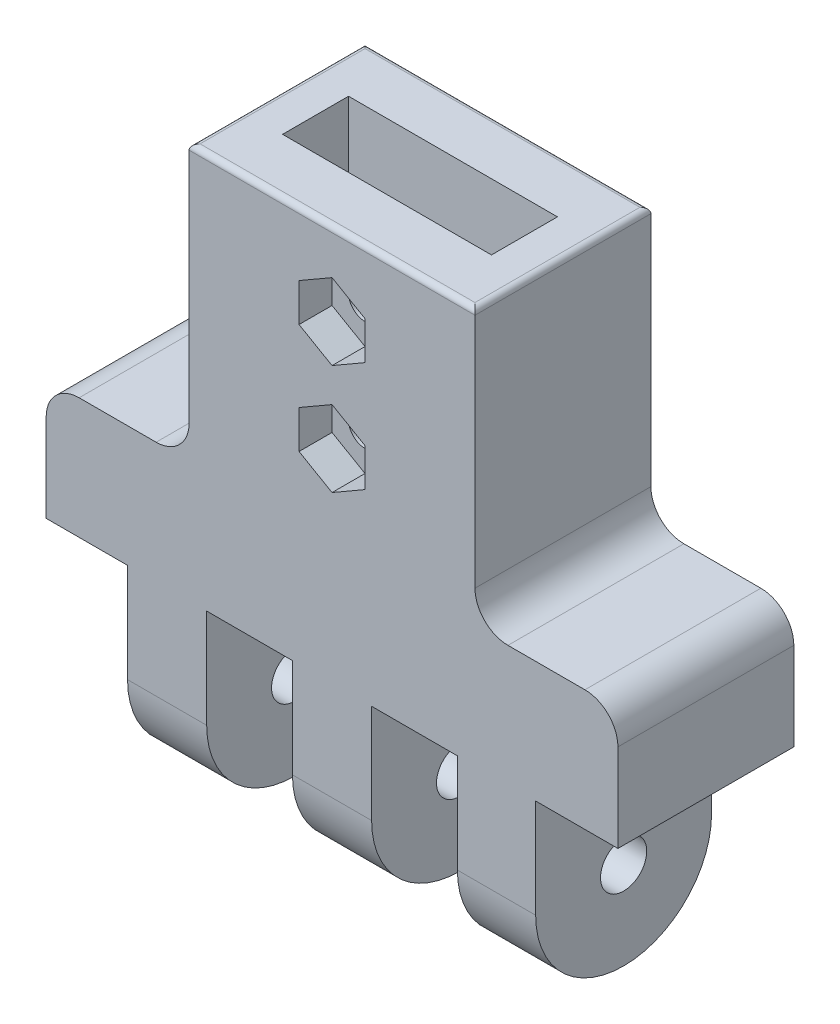
SolidWorks part; units mm, degrees
ref_plane "Front Plane" through (0, 0, 0) normal (0, 0, 1) x (1, 0, 0)
ref_plane "Top Plane" through (0, 0, 0) normal (0, 1, 0) x (1, 0, 0)
ref_plane "Right Plane" through (0, 0, 0) normal (1, 0, 0) x (0, 0, -1)
sketch "Sketch2" plane through (0, 0, 0) normal (1, 0, 0) x (0, 0, -1)
  line L2 (-8, 0) -> (-8, 20)
  line L3 (-8, 20) -> (8, 20)
  line L4 (8, 0) -> (8, 20)
  circle A0 centre (0, 0) radius 2.1
  arc A1 (-8, 0) -> (8, 0) centre (0, 0) ccw
  dimension "D1" = 16
  dimension "D2" = 4.2
  dimension "D3" = 20
extrude "Boss-Extrude1" add sketch "Sketch2" along normal mid plane 52
sketch "Sketch3" plane through (0, 0, 8) normal (0, 0, 1) x (1, 0, 0)
  line L0 (26, 0) -> (-26, 0) construction
  line L1 (-26, -9) -> (-18.6, -9)
  line L2 (-26, -9) -> (-26, 9)
  line L3 (-26, 9) -> (-18.6, 9)
  line L4 (-18.6, -9) -> (-18.6, 9)
  line L5 (-26, -9) -> (-18.6, 9) construction
  line L6 (-26, 9) -> (-18.6, -9) construction
  line L8 (-11.4, -9) -> (-3.6, -9)
  line L9 (-11.4, -9) -> (-11.4, 9)
  line L10 (-11.4, 9) -> (-3.6, 9)
  line L11 (-3.6, -9) -> (-3.6, 9)
  line L12 (-11.4, -9) -> (-3.6, 9) construction
  line L13 (-11.4, 9) -> (-3.6, -9) construction
  line L14 (3.6, -9) -> (11.4, -9)
  line L15 (3.6, -9) -> (3.6, 9)
  line L16 (3.6, 9) -> (11.4, 9)
  line L17 (11.4, -9) -> (11.4, 9)
  line L18 (3.6, -9) -> (11.4, 9) construction
  line L19 (3.6, 9) -> (11.4, -9) construction
  line L20 (-26, 20) -> (-26, 0) construction
  line L21 (26, 20) -> (26, 0) construction
  line L22 (18.519, -9) -> (26, -9)
  line L23 (18.519, -9) -> (18.519, 9)
  line L24 (18.519, 9) -> (26, 9)
  line L25 (26, -9) -> (26, 9)
  line L26 (18.519, -9) -> (26, 9) construction
  line L27 (18.519, 9) -> (26, -9) construction
  point P0 (-22.3, 0)
  point P7 (-7.5, 0)
  point P12 (7.5, 0)
  point P17 (-22.3, 9)
  point P20 (22.2595, 0)
  dimension "D1" = 9
  dimension "D4" = 7.2
  dimension "D6" = 7.2
  dimension "D2" = 7.8
  dimension "D3" = 14.6
extrude "Cut-Extrude1" cut sketch "Sketch3" against normal through all
ref_plane "Plane1" through (0, 20, 0) normal (0, 1, 0) x (1, 0, 0)
sketch "Sketch4" plane through (0, 20, 0) normal (0, 1, 0) x (1, 0, 0)
  line L0 (26, 8) -> (26, -8) construction
  line L1 (13, -8) -> (-13, -8)
  line L2 (13, -8) -> (13, 8)
  line L3 (13, 8) -> (-13, 8)
  line L4 (-13, -8) -> (-13, 8)
  line L5 (13, -8) -> (-13, 8) construction
  line L6 (13, 8) -> (-13, -8) construction
  line L8 (26, -8) -> (-26, -8) construction
  point P0 (0, 0)
  dimension "D1" = 26
  dimension "D2" = 16
  dimension "D3" = 26
extrude "Boss-Extrude2" add sketch "Sketch4" along normal blind 25
ref_plane "Plane2" through (0, 45, 0) normal (0, 1, 0) x (1, 0, 0)
sketch "Sketch5" plane through (0, 45, 0) normal (0, 1, 0) x (1, 0, 0)
  line L0 (13, -8) -> (13, 8) construction
  line L1 (-9.5, 3) -> (9.5, 3)
  line L2 (-9.5, 3) -> (-9.5, -3)
  line L3 (-9.5, -3) -> (9.5, -3)
  line L4 (9.5, 3) -> (9.5, -3)
  line L5 (-9.5, 3) -> (9.5, -3) construction
  line L6 (-9.5, -3) -> (9.5, 3) construction
  line L8 (-13, -8) -> (13, -8) construction
  line L10 (13, 8) -> (-13, 8) construction
  line L11 (13, -8) -> (13, 8) construction
  line L12 (-13, 8) -> (-13, -8) construction
  point P0 (0, 0)
  dimension "D1" = 19
  dimension "D2" = 13
  dimension "D3" = 6
  dimension "D4" = 5
  dimension "D5" = 5
extrude "Cut-Extrude2" cut sketch "Sketch5" against normal blind 25
fillet "Fillet2" radius 3 2 edges at (26, 20, 0) (-26, 20, 0)
sketch "Sketch6" plane through (0, 0, 0) normal (0, 0, 1) x (1, 0, 0)
  line L0 (9.5, 20) -> (9.5, 45) construction
  line L1 (-16.3932, 32.5) -> (15.2785, 32.5) construction
  line L2 (9.5, 20) -> (-9.5, 20) construction
  circle A0 centre (0, 37.5) radius 1.5
  circle A1 centre (0, 27.5) radius 1.5
  dimension "D1" = 3
  dimension "D2" = 9.5
  dimension "D3" = 10
  dimension "D4" = 5
  dimension "D5" = 12.5
extrude "Cut-Extrude3" cut sketch "Sketch6" against normal mid plane 25
fillet "Fillet3" radius 0.5 4 edges at (0, 45, 8) (13, 45, 0) (0, 45, -8) (-13, 45, 0)
fillet "Fillet4" radius 3 2 edges at (13, 20, 0) (-13, 20, 0)
ref_plane "Plane3" through (0, 0, 8) normal (0, 0, 1) x (1, 0, 0)
sketch "Sketch7" plane through (0, 0, 8) normal (0, 0, 1) x (1, 0, 0)
  line L1 (3, 35.7679) -> (3, 39.2321)
  line L2 (3, 39.2321) -> (0, 40.9641)
  line L3 (0, 40.9641) -> (-3, 39.2321)
  line L4 (-3, 39.2321) -> (-3, 35.7679)
  line L5 (-3, 35.7679) -> (0, 34.0359)
  line L6 (0, 34.0359) -> (3, 35.7679)
  line L7 (3, 25.7679) -> (3, 29.2321)
  line L8 (3, 29.2321) -> (0, 30.9641)
  line L9 (0, 30.9641) -> (-3, 29.2321)
  line L10 (-3, 29.2321) -> (-3, 25.7679)
  line L11 (-3, 25.7679) -> (0, 24.0359)
  line L12 (0, 24.0359) -> (3, 25.7679)
  circle A0 centre (0, 37.5) radius 3 construction
  circle A1 centre (0, 27.5) radius 3 construction
  circle A2 centre (0, 27.5) radius 1.5 construction
  dimension "D1" = 6
  dimension "D2" = 6
extrude "Cut-Extrude4" cut sketch "Sketch7" against normal blind 3
equation "\"hingewidth\"=7.2"
equation "\"fingerwidth\"=10.5"
equation "\"gapwidth\"=7.4"
equation "\"D4@Sketch3\"=\"hingewidth\""
equation "\"D6@Sketch3\"=\"hingewidth\""
